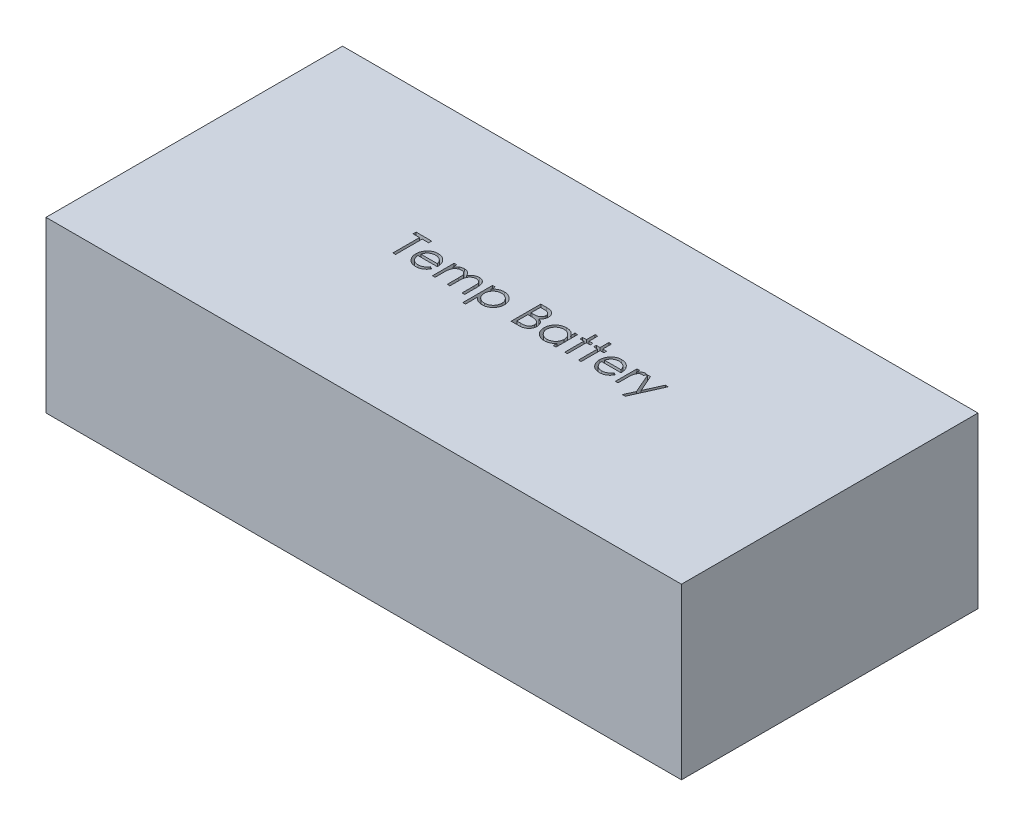
SolidWorks part; units mm, degrees
ref_plane "Front Plane" through (0, 0, 0) normal (0, 0, 1) x (1, 0, 0)
ref_plane "Top Plane" through (0, 0, 0) normal (0, 1, 0) x (1, 0, 0)
ref_plane "Right Plane" through (0, 0, 0) normal (1, 0, 0) x (0, 0, -1)
sketch "Sketch1" plane through (0, 0, 0) normal (0, 1, 0) x (1, 0, 0)
  line L1 (37.5, -17.5) -> (-37.5, -17.5)
  line L2 (37.5, -17.5) -> (37.5, 17.5)
  line L3 (37.5, 17.5) -> (-37.5, 17.5)
  line L4 (-37.5, -17.5) -> (-37.5, 17.5)
  line L5 (37.5, -17.5) -> (-37.5, 17.5) construction
  line L6 (37.5, 17.5) -> (-37.5, -17.5) construction
  point P0 (0, 0)
  dimension "D1" = 75
  dimension "D2" = 35
extrude "Boss-Extrude1" add sketch "Sketch1" along normal blind 20
sketch "Sketch2" plane through (0, 20, 0) normal (0, 1, 0) x (1, 0, 0)
  text T0 "Temp Battery"
extrude "Cut-Extrude1" cut sketch "Sketch2" against normal blind 4
